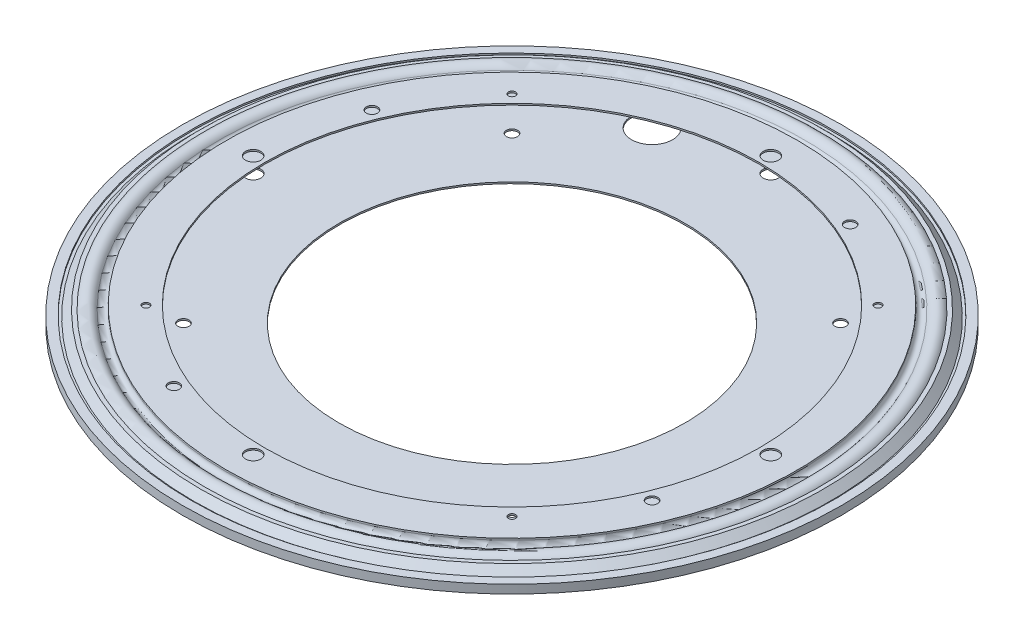
SolidWorks part; units mm, degrees
note: The reader was unsure of these and kept them because the rebuilt part matched: shared geometry of "Sketch1<7>".
ref_plane "Front" through (0, 0, 0) normal (0, 0, 1) x (1, 0, 0)
ref_plane "Top" through (0, 0, 0) normal (0, 1, 0) x (1, 0, 0)
ref_plane "Right" through (0, 0, 0) normal (1, 0, 0) x (0, 0, -1)
sketch "Sketch1" plane through (0, 0, 0) normal (0, 0, 1) x (1, 0, 0)
  line L0 (0, 21.7127) -> (0, -25.7345) construction
  line L1 (139.7, 7.2103) -> (139.7, -7.2103) construction
  line L2 (132.6654, -3.175) -> (132.6654, -3.9751)
  line L3 (132.6654, 3.175) -> (132.6654, 3.9751)
  line L4 (146.7346, -3.175) -> (146.7346, -3.9751)
  line L5 (146.7346, -3.9751) -> (153.2001, -3.9751)
  line L6 (-2.2827, 0) -> (4.7936, 0) construction
  line L7 (132.6654, 3.9751) -> (114.8969, 3.9751)
  line L8 (153.2001, -3.9751) -> (153.2001, 0)
  line L9 (132.6654, -3.9751) -> (80.391, -3.9751)
  line L10 (87.3679, 0) -> (192.0321, 0) construction
  line L11 (153.2001, 0) -> (149.1361, 0)
  line L12 (151.1681, -0.889) -> (147.9659, -0.889)
  line L13 (147.9659, -0.889) -> (144.747, 2.3299)
  line L14 (144.747, 2.3299) -> (142.9207, 2.3299)
  arc A0 (136.3353, -2.1167) -> (132.6654, -3.175) centre (134.653, -3.175) ccw
  arc A1 (136.3353, -2.1167) -> (143.0647, -2.1167) centre (139.7, 0) ccw
  arc A2 (143.0647, -2.1167) -> (146.7346, -3.175) centre (144.747, -3.175) cw
  circle A3 centre (139.7, 0) radius 3.9751 construction
  arc A4 (136.3353, 2.1167) -> (142.9207, 2.3299) centre (139.7, 0) cw
  arc A6 (136.3353, 2.1167) -> (132.6654, 3.175) centre (134.653, 3.175) cw
  point P34 (151.1681, 0)
  dimension "D1" = 160.782
  dimension "D5" = 7.9502
  dimension "D7" = 3.9751
  dimension "D6" = 7.9502
  dimension "D3" = 279.4
  dimension "D11" = 1.905
  dimension "D2" = 306.4002
  dimension "D4" = 229.7938
  dimension "D8" = 3.175
  dimension "D9" = 4.064
  dimension "D10" = 0.889
  dimension "D12" = 135
revolve "Revolve-Thin1" add sketch "Sketch1" angle 360 about L0
revolve "Revolve-Thin2" add sketch "Sketch1<7>" angle 360 about L0
sketch "Sketch1<7>" plane through (0, 0, 0) normal (0, 0, 1) x (1, 0, 0) same geometry as "Sketch1"
sketch "Sketch2" plane through (0, 0, 0) normal (0, 0, 1) x (1, 0, 0)
  line L0 (139.7, 7.2103) -> (139.7, -7.2103) construction
  line L1 (139.7, 3.1877) -> (139.7, -3.1877)
  line L2 (139.7, 5.3554) -> (139.7, -5.2305) construction
  line L3 (147.4712, -3.2385) -> (-147.4712, -3.2385) construction
  arc A0 (139.7, 3.1877) -> (139.7, -3.1877) centre (139.7, 0) cw
  circle A1 centre (139.7, 0) radius 3.9751 construction
  dimension "D1" = 0.0508
revolve "Revolve1" add sketch "Sketch2" angle 360 about L2
pattern_circular "CirPattern1" count 12 over 360 about axis through (0, 0, 0) along (0, 1, 0) of bodies 128
sketch "Sketch3" plane through (0, -3.2385, 0) normal (0, 1, 0) x (-1, 0, 0)
  line L0 (0, 0) -> (0, 94.742) construction
  line L1 (0, 0) -> (-46.0201, 111.1023) construction
  line L2 (-14.0129, -5.8043) -> (14.0129, 5.8043) construction
  circle A0 centre (-46.0201, 111.1023) radius 9.525
  circle A1 centre (46.0201, -111.1023) radius 9.525
  dimension "D1" = 19.05
  dimension "D3" = 240.5126
  dimension "D2" = 22.5
extrude "Cut-Extrude1" cut sketch "Sketch3" against normal through all
hole_wizard "9/32 (0.281250) Diameter Hole1" positions "Sketch5" profile "Sketch4" hole size "9/32" standard "Ansi Inch" end condition up to next
sketch "Sketch5" plane through (0, 3.9751, 0) normal (0, 1, 0) x (-1, 0, 0)
  line L0 (19.7529, 0) -> (-13.4622, 0) construction
  point P0 (0, -120.2563)
  dimension "D1" = 240.5126
sketch "Sketch4" plane through (0, 3.9751, -120.2563) normal (1, 0, 0) x (0, 0, 1)
  line L0 (0, 0) -> (0, 0.7366)
  line L1 (0, 0.7366) -> (3.5719, 0.7366)
  line L2 (3.5719, 0.7366) -> (3.5719, 0)
  line L5 (3.5719, 0) -> (0, 0)
  line L11 (0, -6.35) -> (0, 107.95) construction
  dimension "Thru Hole Dia." = 7.1437
  dimension "Thru Hole Depth" = 0.7366
pattern_circular "CirPattern2" count 4 over 360 about axis through (0, 0, 0) along (0, 1, 0) of "9/32 (0.281250) Diameter Hole1"
hole_wizard "9/32 (0.281250) Diameter Hole2" positions "Sketch7" profile "Sketch6" hole size "9/32" standard "Ansi Inch"
sketch "Sketch7" plane through (0, -3.2385, 0) normal (0, 1, 0) x (-1, 0, 0)
  line L0 (8.178, 0) -> (-7.4231, 0) construction
  point P0 (0, -120.2563)
  dimension "D1" = 240.5126
sketch "Sketch6" plane through (0, -3.2385, -120.2563) normal (1, 0, 0) x (0, 0, 1)
  line L0 (0, 0) -> (0, 10.2742)
  line L1 (0, 10.2742) -> (3.5719, 8.128)
  line L2 (3.5719, 8.128) -> (3.5719, 0)
  line L5 (3.5719, 0) -> (0, 0)
  line L10 (0, 10.2742) -> (-3.5719, 8.128) construction
  line L11 (0, -6.35) -> (0, 107.95) construction
  dimension "Hole Dia." = 7.1437
  dimension "Hole Depth" = 8.128
  dimension "Drill Angle" = 118
pattern_circular "CirPattern3" count 4 over 360 about axis through (0, 0, 0) along (0, 1, 0) of "9/32 (0.281250) Diameter Hole2"
hole_wizard "13/64 (0.203130) Diameter Hole1" positions "Sketch9" profile "Sketch8" hole size "13/64" standard "Ansi Inch" end condition up to next
sketch "Sketch9" plane through (0, 3.9751, 0) normal (0, 1, 0) x (-1, 0, 0)
  line L0 (0, 0) -> (-46.0201, -111.1023) construction
  line L1 (-11.8597, 4.9125) -> (11.8597, -4.9125) construction
  line L2 (0, 0) -> (0, -33.4677) construction
  point P0 (-46.0201, -111.1023)
  dimension "D1" = 22.5
  dimension "D2" = 240.5126
sketch "Sketch8" plane through (46.0201, 3.9751, -111.1023) normal (1, 0, 0) x (0, 0, 1)
  line L0 (0, 0) -> (0, 0.7366)
  line L1 (0, 0.7366) -> (2.5798, 0.7366)
  line L2 (2.5798, 0.7366) -> (2.5798, 0)
  line L5 (2.5798, 0) -> (0, 0)
  line L11 (0, -6.35) -> (0, 107.95) construction
  dimension "Thru Hole Dia." = 5.1595
  dimension "Thru Hole Depth" = 0.7366
pattern_circular "CirPattern4" count 4 over 360 about axis through (0, 0, 0) along (0, 1, 0) of "13/64 (0.203130) Diameter Hole1"
hole_wizard "1/8 (0.125000) Diameter Hole1" positions "Sketch11" profile "Sketch10" hole size "1/8" standard "Ansi Inch" end condition up to next
sketch "Sketch11" plane through (0, 3.9751, 0) normal (0, 1, 0) x (-1, 0, 0)
  line L0 (0, 0) -> (0, -44.4572) construction
  line L1 (0, 0) -> (-85.034, -85.034) construction
  line L2 (14.5165, -14.5165) -> (-14.5165, 14.5165) construction
  point P0 (-85.034, -85.034)
  dimension "D1" = 45
  dimension "D2" = 240.5126
sketch "Sketch10" plane through (85.034, 3.9751, -85.034) normal (1, 0, 0) x (0, 0, 1)
  line L0 (0, 0) -> (0, 0.7366)
  line L1 (0, 0.7366) -> (1.651, 0.7366)
  line L2 (1.651, 0.7366) -> (1.651, 0)
  line L5 (1.651, 0) -> (0, 0)
  line L11 (0, -6.35) -> (0, 107.95) construction
  dimension "Thru Hole Dia." = 3.302
  dimension "Thru Hole Depth" = 0.7366
pattern_circular "CirPattern5" count 4 over 360 about axis through (0, 0, 0) along (0, 1, 0) of "1/8 (0.125000) Diameter Hole1"
hole_wizard "13/64 (0.203130) Diameter Hole2" positions "Sketch13" profile "Sketch12" hole size "13/64" standard "Ansi Inch" end condition up to next
sketch "Sketch13" plane through (0, -3.2385, 0) normal (0, 1, 0) x (-1, 0, 0)
  line L0 (0, 0) -> (-76.3322, -76.3322) construction
  line L1 (0, 0) -> (0, -45.7892) construction
  line L2 (16.5883, -16.5883) -> (-16.5883, 16.5883) construction
  point P0 (-76.3322, -76.3322)
  dimension "D1" = 45
  dimension "D2" = 215.9
sketch "Sketch12" plane through (76.3322, -3.2385, -76.3322) normal (1, 0, 0) x (0, 0, 1)
  line L0 (0, 0) -> (0, 0.7366)
  line L1 (0, 0.7366) -> (2.5798, 0.7366)
  line L2 (2.5798, 0.7366) -> (2.5798, 0)
  line L5 (2.5798, 0) -> (0, 0)
  line L11 (0, -6.35) -> (0, 107.95) construction
  dimension "Thru Hole Dia." = 5.1595
  dimension "Thru Hole Depth" = 0.7366
pattern_circular "CirPattern6" count 4 over 360 about axis through (0, 0, 0) along (0, 1, 0) of "13/64 (0.203130) Diameter Hole2"
equation "\"D7@Sketch1\"=\"D5@Sketch1\"/2"
